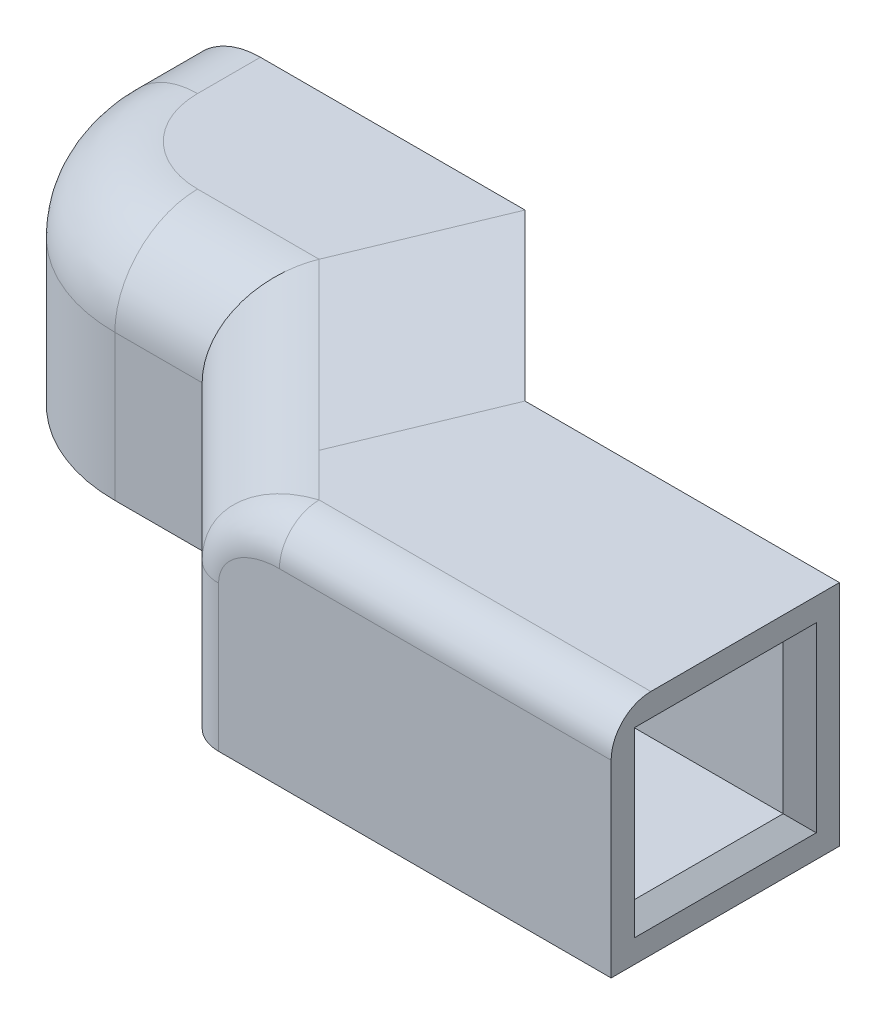
SolidWorks part; units mm, degrees
ref_plane "Front Plane" through (0, 0, 0) normal (0, 0, 1) x (1, 0, 0)
ref_plane "Top Plane" through (0, 0, 0) normal (0, 1, 0) x (1, 0, 0)
ref_plane "Right Plane" through (0, 0, 0) normal (1, 0, 0) x (0, 0, -1)
sketch "Sketch1" plane through (0, 0, 0) normal (1, 0, 0) x (0, 0, -1)
  line L0 (-2.4, 11.4) -> (11.4, 11.4)
  line L1 (0, 0) -> (9, 0)
  line L2 (0, 0) -> (0, 9)
  line L3 (0, 9) -> (9, 9)
  line L4 (9, 0) -> (9, 9)
  line L5 (11.4, -2.4) -> (11.4, 11.4)
  line L6 (-2.4, -2.4) -> (11.4, -2.4)
  line L7 (-2.4, -2.4) -> (-2.4, 11.4)
  dimension "D1" = 9
  dimension "D2" = 2.4
sketch "Sketch2" plane through (0, 0, 0) normal (0, 1, 0) x (1, 0, 0)
  line L1 (0, 9) -> (-20, 9)
  line L2 (-20, 9) -> (-20, 19) construction
  line L3 (-20, 19) -> (-30, 19) construction
  line L4 (-20, 9) -> (-30, 19)
  line L5 (-30, 19) -> (-50, 19)
  dimension "D2" = 10
  dimension "D3" = 20
  dimension "D4" = 20
sweep "Sweep1" add profiles "Sketch1" path "Sketch2"
sketch "Sketch6" plane through (-50, 0, 0) normal (-1, 0, 0) x (0, 0, 1)
  line L1 (-10, 9) -> (-19, 9)
  line L2 (-10, 9) -> (-10, 0)
  line L3 (-10, 0) -> (-19, 0)
  line L4 (-19, 9) -> (-19, 0)
extrude "Boss-Extrude1" add sketch "Sketch6" against normal up to next
fillet "Fillet1" radius 10 1 edges at (-50, 4.5, -7.6)
fillet "Fillet2" radius 5 4 edges at (-50, 11.4, -19.5) (-47.0711, 11.4, -10.5289) (-29.722, 11.4, -2.6) (-37.361, 11.4, -7.6)
fillet "Fillet3" radius 2.4 3 edges at (-8.8255, 11.4, 2.4) (-22.651, 9.9355, 2.4) (-24.722, 2, 2.4)
sketch "Sketch7" plane through (0, 0, -9) normal (0, 0, 1) x (1, 0, 0)
  line L1 (-8.2, 6.75) -> (-12.7, 6.75)
  line L2 (-8.2, 6.75) -> (-8.2, 2.25)
  line L3 (-8.2, 2.25) -> (-12.7, 2.25)
  line L4 (-12.7, 6.75) -> (-12.7, 2.25)
  line L5 (-10.45, 6.75) -> (-10.45, 9) construction
  line L7 (-10.45, 2.25) -> (-10.45, 0) construction
  line L9 (0, 9) -> (-20, 9) construction
  line L10 (0, 0) -> (-20, 0) construction
  line L11 (0, 9) -> (0, 0) construction
  point P4 (0, 0)
  point P9 (0, 0)
  dimension "D1" = 4.5
  dimension "D2" = 8.2
extrude "Cut-Extrude1" cut sketch "Sketch7" against normal up to next contours L2 L1 L4 L3
chamfer "Chamfer1" distance 1 angle 45 4 edges at (0, 4.5, -9) (0, 9, -4.5) (0, 4.5, 0) (0, 0, -4.5)
equation "\"Tube_ID\"= 9"
equation "\"D1@Sketch1\"=\"Tube_ID\""
equation "\"wall_Thickness\"=2.4"
equation "\"D2@Sketch1\"=\"wall_Thickness\""
equation "\"Extension_Length\"= 20"
equation "\"D3@Sketch2\"=\"Extension_Length\""
equation "\"Offset_Amount\"=10"
equation "\"D2@Sketch2\"=\"Offset_Amount\""
equation "\"Socket_Depth\"=20"
equation "\"D4@Sketch2\"=\"Socket_Depth\""
equation "\"Overall_Length\"= \"Extension_Length\" + \"Offset_Amount\" + \"Socket_Depth\""
